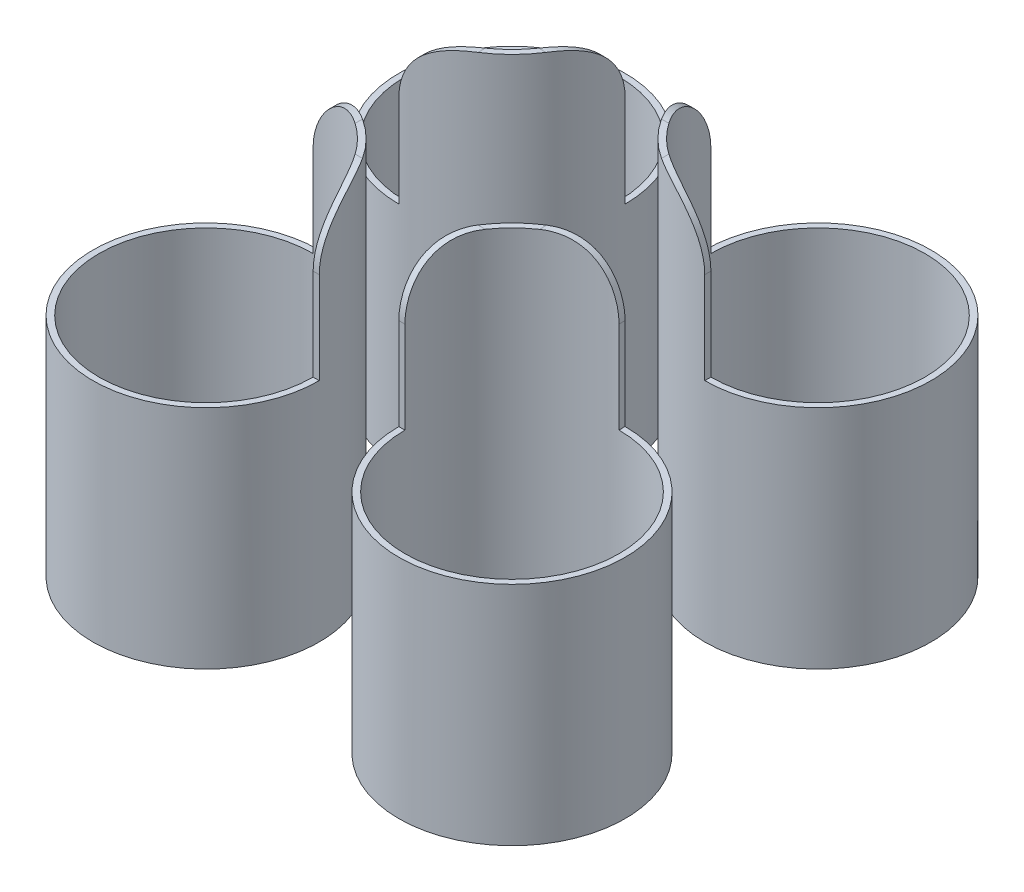
SolidWorks part; units mm, degrees
ref_plane "Front Plane" through (0, 0, 0) normal (0, 0, 1) x (1, 0, 0)
ref_plane "Top Plane" through (0, 0, 0) normal (0, 1, 0) x (1, 0, 0)
ref_plane "Right Plane" through (0, 0, 0) normal (1, 0, 0) x (0, 0, -1)
sketch "Sketch1" plane through (0, 0, 0) normal (0, 1, 0) x (1, 0, 0)
  circle A2 centre (0, 0) radius 18.5
  circle A3 centre (0, 0) radius 18.5
  circle A5 centre (-7, -7) radius 4.4
  circle A6 centre (-7, -7) radius 4.4
  circle A8 centre (-7, 7) radius 4.4
  circle A9 centre (-7, 7) radius 4.4
  circle A11 centre (7, 7) radius 4.4
  circle A12 centre (7, 7) radius 4.4
  circle A14 centre (7, -7) radius 4.4
  circle A15 centre (7, -7) radius 4.4
  circle A17 centre (-7, 43) radius 4.4
  circle A18 centre (-7, 43) radius 4.4
  circle A20 centre (-7, 57) radius 4.4
  circle A21 centre (-7, 57) radius 4.4
  circle A23 centre (7, 43) radius 4.4
  circle A24 centre (7, 43) radius 4.4
  circle A26 centre (7, 57) radius 4.4
  circle A27 centre (7, 57) radius 4.4
  circle A29 centre (43, -7) radius 4.4
  circle A30 centre (43, -7) radius 4.4
  circle A32 centre (43, 7) radius 4.4
  circle A33 centre (43, 7) radius 4.4
  circle A35 centre (57, -7) radius 4.4
  circle A36 centre (57, -7) radius 4.4
  circle A38 centre (57, 7) radius 4.4
  circle A39 centre (57, 7) radius 4.4
  circle A41 centre (43, 43) radius 4.4
  circle A42 centre (43, 43) radius 4.4
  circle A44 centre (57, 43) radius 4.4
  circle A45 centre (57, 43) radius 4.4
  circle A47 centre (43, 57) radius 4.4
  circle A48 centre (43, 57) radius 4.4
  circle A50 centre (57, 57) radius 4.4
  circle A51 centre (57, 57) radius 4.4
  circle A53 centre (0, 50) radius 18.5
  circle A54 centre (0, 50) radius 18.5
  circle A56 centre (50, 0) radius 18.5
  circle A57 centre (50, 0) radius 18.5
  circle A59 centre (50, 50) radius 18.5
  circle A60 centre (50, 50) radius 18.5
  dimension "D1" = 1
  dimension "D2" = 0.8
  dimension "D3" = 0.8
  dimension "D4" = 0.8
  dimension "D5" = 0.8
  dimension "D6" = 0.8
  dimension "D7" = 0.8
  dimension "D8" = 0.8
  dimension "D9" = 0.8
  dimension "D10" = 0.8
  dimension "D11" = 0.8
  dimension "D12" = 0.8
  dimension "D13" = 0.8
  dimension "D14" = 0.8
  dimension "D15" = 0.8
  dimension "D16" = 0.8
  dimension "D17" = 0.8
  dimension "D18" = 1
  dimension "D19" = 1
  dimension "D20" = 1
extrude "Boss-Extrude1" add sketch "Sketch1" along normal blind 2
sketch "Sketch2" plane through (0, 2, 0) normal (0, 1, 0) x (1, 0, 0)
  circle A0 centre (0, 0) radius 17.5
  circle A1 centre (0, 0) radius 18.5
  circle A2 centre (0, 0) radius 18.5
  circle A3 centre (50, 0) radius 18.5 construction
  circle A4 centre (50, 0) radius 18.5
  circle A5 centre (50, 0) radius 17.5
  circle A6 centre (50, 50) radius 17.5
  circle A7 centre (50, 50) radius 18.5
  circle A8 centre (50, 50) radius 18.5
  circle A9 centre (0, 50) radius 17.5
  circle A10 centre (0, 50) radius 18.5
  circle A11 centre (0, 50) radius 18.5
  dimension "D1" = 0
  dimension "D2" = 1
  dimension "D3" = 1
  dimension "D4" = 0
  dimension "D5" = 1
  dimension "D6" = 0
  dimension "D7" = 1
extrude "Boss-Extrude2" add sketch "Sketch2" along normal offset from surface (35 mm away) 2 offset beyond the face yes
sketch "Sketch3" plane through (0, 37, 0) normal (0, 1, 0) x (1, 0, 0)
  line L0 (50, 31.5) -> (50, 32.5)
  line L1 (31.5, 50) -> (32.5, 50)
  line L2 (18.5, 50) -> (17.5, 50)
  line L3 (0, 32.5) -> (0, 31.5)
  line L4 (0, 18.5) -> (0, 17.5)
  line L5 (17.5, 0) -> (18.5, 0)
  line L6 (49.9646, 18.6067) -> (50, 17.5)
  line L7 (31.5, 0) -> (32.5, 0)
  circle A0 centre (50, 50) radius 18.5 construction
  arc A1 (31.5, 50) -> (50, 31.5) centre (50, 50) ccw
  circle A2 centre (50, 50) radius 17.5 construction
  arc A3 (32.5, 50) -> (50, 32.5) centre (50, 50) ccw
  circle A4 centre (50, 0) radius 18.5 construction
  arc A5 (49.968, 18.5) -> (31.5, 0) centre (50, 0) ccw
  circle A6 centre (50, 0) radius 17.5 construction
  arc A7 (50, 17.5) -> (32.5, 0) centre (50, 0) ccw
  circle A8 centre (0, 0) radius 18.5 construction
  arc A9 (18.5, 0) -> (0, 18.5) centre (0, 0) ccw
  circle A10 centre (0, 0) radius 17.5 construction
  arc A11 (17.5, 0) -> (0, 17.5) centre (0, 0) ccw
  circle A12 centre (0, 50) radius 18.5 construction
  arc A13 (0, 31.5) -> (18.5, 50) centre (0, 50) ccw
  circle A14 centre (0, 50) radius 17.5 construction
  arc A15 (0, 32.5) -> (17.5, 50) centre (0, 50) ccw
  circle M1 centre (50, 50) radius 17.5
  circle M2 centre (50, 50) radius 18.5
extrude "Boss-Extrude3" add sketch "Sketch3" along normal blind 25 contours A7 L6 A5 L7 | L1 L0 M2 M1 | A11 L5 A9 L4 | A15 L2 A13 L3 region at (37.1035, 37, -37.1035) region at (12.8965, 37, -12.8965) region at (49.7225, 37, -17.9916)
fillet "Fillet1" radius 10 2 edges at (32, 62, 0) (49.984, 62, -18)
fillet "Fillet2" radius 10 2 edges at (32, 62, -50) (50, 62, -32)
fillet "Fillet3" radius 10 2 edges at (0, 62, -32) (18, 62, -50)
fillet "Fillet4" radius 10 2 edges at (18, 62, 0) (0, 62, -18)
